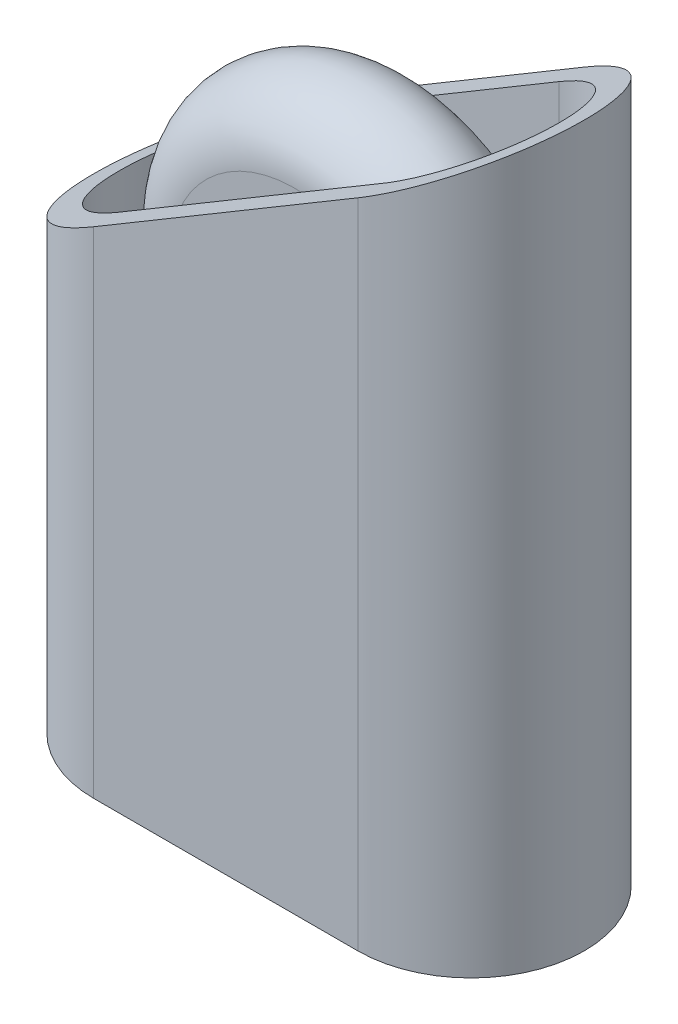
SolidWorks part; units mm, degrees
ref_plane "前视基准面" through (0, 0, 0) normal (0, 0, 1) x (1, 0, 0)
ref_plane "上视基准面" through (0, 0, 0) normal (0, 1, 0) x (1, 0, 0)
ref_plane "右视基准面" through (0, 0, 0) normal (1, 0, 0) x (0, 0, -1)
other "Configuration Table"
sketch "草图1" plane through (0, 0, 0) normal (0, 1, 0) x (1, 0, 0)
  line L0 (0, 0) -> (10.5, 0) construction
  line L1 (0, 3.5) -> (10.5, 3.5)
  line L2 (0, -3.5) -> (10.5, -3.5)
  arc A0 (0, 3.5) -> (0, -3.5) centre (0, 0) ccw
  arc A1 (10.5, -3.5) -> (10.5, 3.5) centre (10.5, 0) ccw
  point P3 (5.25, 0)
  dimension "D1" = 3.5
  dimension "D2" = 10.5
extrude "拉伸-薄壁1" add sketch "草图1" along normal blind 30 thin thin type one direction wall 1
sketch "草图2" plane through (0, 0, 0) normal (0, 0, 1) x (1, 0, 0)
  line L0 (-4.5, 17) -> (15, 28.6)
  line L1 (-4.5, 30) -> (-4.5, 0) construction
  line L2 (15, 0) -> (15, 30) construction
  line L3 (15, 28.6) -> (15, 30)
  line L4 (15, 30) -> (-4.5, 30)
  line L5 (-4.5, 30) -> (-4.5, 17)
  dimension "D1" = 17
  dimension "D2" = 28.6
extrude "切除-拉伸1" cut sketch "草图2" against normal mid plane 10
sketch "草图3" plane through (0, 0, 0) normal (0, 0, 1) x (1, 0, 0)
  line L0 (10.5, 25.9231) -> (10.5, 0) construction
  line L2 (0, 0) -> (10.5, 0) construction
  circle A0 centre (6, 18) radius 3.5
  point P3 (0, 0)
  point P4 (0, 0)
  dimension "D1" = 7
  dimension "D2" = 18
  dimension "D3" = 4.5
extrude "凸台-拉伸1" add sketch "草图3" along normal mid plane 7
sketch "草图4" plane through (0, 0, 0) normal (0, 0, 1) x (1, 0, 0)
  circle A0 centre (6, 18) radius 3.5 construction
  circle A1 centre (6, 18) radius 3.5
  circle A2 centre (6, 18) radius 3.75
  circle A3 centre (6, 18) radius 7.5
  dimension "D1" = 7.5
  dimension "D2" = 15
extrude "凸台-拉伸2" add sketch "草图4" along normal mid plane 5 separate body contours A3 A2 region at (-1.2879, 18, 0)
fillet "圆角2" 2 edges at (13.5, 18, -2.5) (13.5, 18, 2.5) type full round first side face at (9.75, 18, -2.5) second side face at (9.75, 18, 2.5) middle face at (13.5, 18, 2.5)
